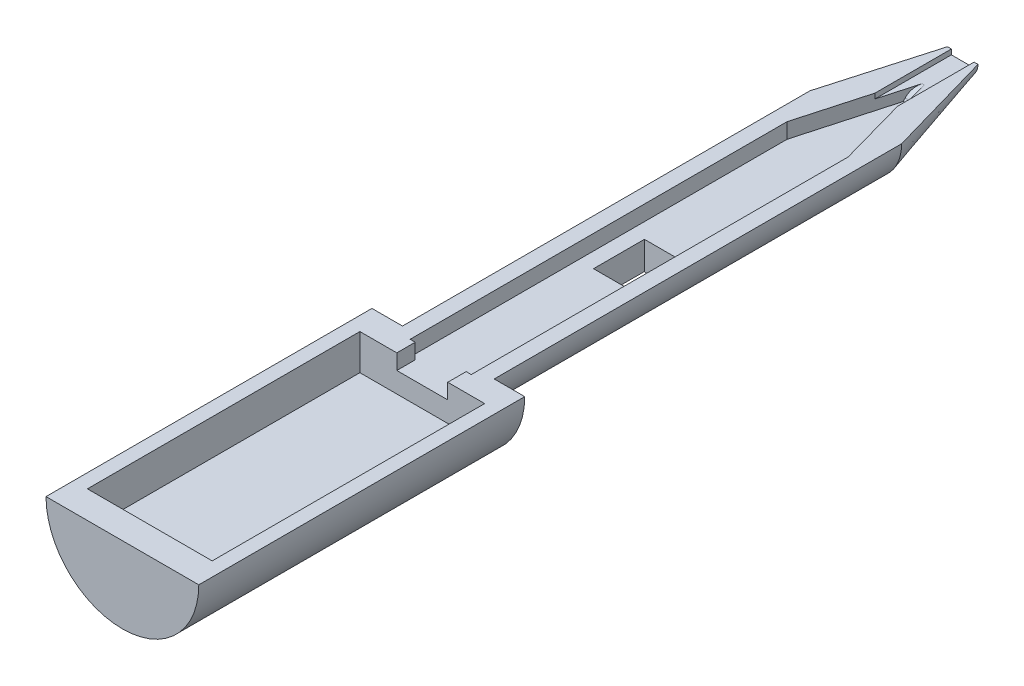
SolidWorks part; units mm, degrees
ref_plane "Front Plane" through (0, 0, 0) normal (0, 0, 1) x (1, 0, 0)
ref_plane "Top Plane" through (0, 0, 0) normal (0, 1, 0) x (1, 0, 0)
ref_plane "Right Plane" through (0, 0, 0) normal (1, 0, 0) x (0, 0, -1)
sketch "Sketch2" plane through (0, 0, 0) normal (0, 1, 0) x (1, 0, 0)
  line L0 (0, 0) -> (-15, 0)
  line L1 (-15, 0) -> (-15, 64)
  line L2 (-15, 64) -> (-9, 64)
  line L3 (-9, 64) -> (-9, 144)
  line L4 (-9, 144) -> (-3, 165)
  line L5 (-3, 165) -> (0, 165)
  line L6 (0, 165) -> (0, 0)
  dimension "D1" = 15
  dimension "D2" = 64
  dimension "D3" = 80
  dimension "D4" = 9
  dimension "D5" = 101
  dimension "D6" = 3
revolve "Revolve1" add sketch "Sketch2" angle 180 about L6
sketch "Sketch3" plane through (0, 0, 0) normal (0, 1, 0) x (1, 0, 0)
  line L0 (-12.25, 5.3825) -> (12.25, 5.3825)
  line L1 (12.25, 5.3825) -> (12.25, 58.8825)
  line L2 (12.25, 58.8825) -> (-12.25, 58.8825)
  line L3 (-12.25, 58.8825) -> (-12.25, 5.3825)
  point P2 (0, 5.3825)
  dimension "D1" = 24.5
  dimension "D2" = 53.5
extrude "Cut-Extrude1" cut sketch "Sketch3" against normal blind 7
sketch "Sketch4" plane through (0, 0, 0) normal (0, 1, 0) x (1, 0, 0)
  line L0 (-6, 62.5) -> (6, 62.5)
  line L1 (6, 62.5) -> (6, 136.5)
  line L2 (6, 136.5) -> (1.25, 153.5)
  line L3 (1.25, 153.5) -> (-1.25, 153.5)
  line L4 (-1.25, 153.5) -> (-6, 136.5)
  line L5 (-6, 136.5) -> (-6, 62.5)
  line L6 (-3, 165) -> (3, 165) construction
  point P7 (0, 153.5)
  point P8 (0, 62.5)
  point P15 (0, 165)
  dimension "D1" = 2.5
  dimension "D2" = 74
  dimension "D3" = 91
  dimension "D4" = 11.5
  dimension "D5" = 12
extrude "Cut-Extrude2" cut sketch "Sketch4" against normal blind 3
sketch "Sketch5" plane through (0, 0, 0) normal (0, 1, 0) x (1, 0, 0)
  line L0 (-5, 62.5) -> (-5, 58.8825)
  line L1 (-6, 62.5) -> (6, 62.5) construction
  line L2 (12.25, 58.8825) -> (-12.25, 58.8825) construction
  line L3 (-5, 58.8825) -> (-2.5, 58.8825)
  line L4 (-2.5, 58.8825) -> (-2.5, 62.5)
  line L5 (-6, 62.5) -> (6, 62.5) construction
  line L6 (-2.5, 62.5) -> (-5, 62.5)
  line L7 (2.5, 62.5) -> (2.5, 58.8825)
  line L8 (2.5, 58.8825) -> (5, 58.8825)
  line L9 (5, 58.8825) -> (5, 62.5)
  line L10 (5, 62.5) -> (2.5, 62.5)
  dimension "D1" = 2.5
  dimension "D2" = 2.5
  dimension "D3" = 1
  dimension "D4" = 1
extrude "Cut-Extrude3" cut sketch "Sketch5" against normal up to surface (3 mm away) up to face at (0, -3, -117.5)
sketch "Sketch6" plane through (0, -3, 0) normal (0, 1, 0) x (1, 0, 0)
  line L0 (-3, 105.5) -> (-3, 95.5)
  line L1 (-3, 95.5) -> (3, 95.5)
  line L2 (3, 95.5) -> (3, 105.5)
  line L3 (3, 105.5) -> (-3, 105.5)
  line L4 (-2.5, 62.5) -> (2.5, 62.5) construction
  point P4 (0, 105.5)
  point P8 (0, 95.5)
  dimension "D1" = 10
  dimension "D2" = 6
  dimension "D3" = 43
extrude "Cut-Extrude4" cut sketch "Sketch6" against normal up to surface (5.4853 mm away) up to face at (0, -4.5, -104)
sketch "Sketch7" plane through (0, 0, 0) normal (0, 1, 0) x (1, 0, 0)
  line L0 (-2.2279, 150) -> (-2.2279, 165)
  line L1 (-1.25, 153.5) -> (-6, 136.5) construction
  line L2 (-3, 165) -> (3, 165) construction
  line L3 (-2.2279, 165) -> (2.2279, 165)
  line L4 (2.2279, 165) -> (2.2279, 150)
  line L5 (6, 136.5) -> (1.25, 153.5) construction
  line L6 (2.2279, 150) -> (-2.2279, 150)
  point P6 (0, 165)
  point P11 (0, 150)
  dimension "D1" = 15
extrude "Cut-Extrude5" cut sketch "Sketch7" against normal blind 1
sketch "Sketch8" plane through (0, 0, 0) normal (0, 1, 0) x (1, 0, 0)
  line L1 (-2.5, 62.5) -> (2.5, 62.5)
  line L2 (-2.5, 62.5) -> (-2.5, 58.8825)
  line L3 (-2.5, 58.8825) -> (2.5, 58.8825)
  line L4 (2.5, 62.5) -> (2.5, 58.8825)
extrude "Cut-Extrude6" cut sketch "Sketch8" against normal up to surface (3 mm away) up to face at (0, -3, -100.5)
chamfer "Chamfer10" distance 2 angle 60 1 edges at (0, -1, -153.5) first distance on face at (0, -1, -156.1667)
fillet "Fillet1" radius 3 1 edges at (0, -1, -155.5)
